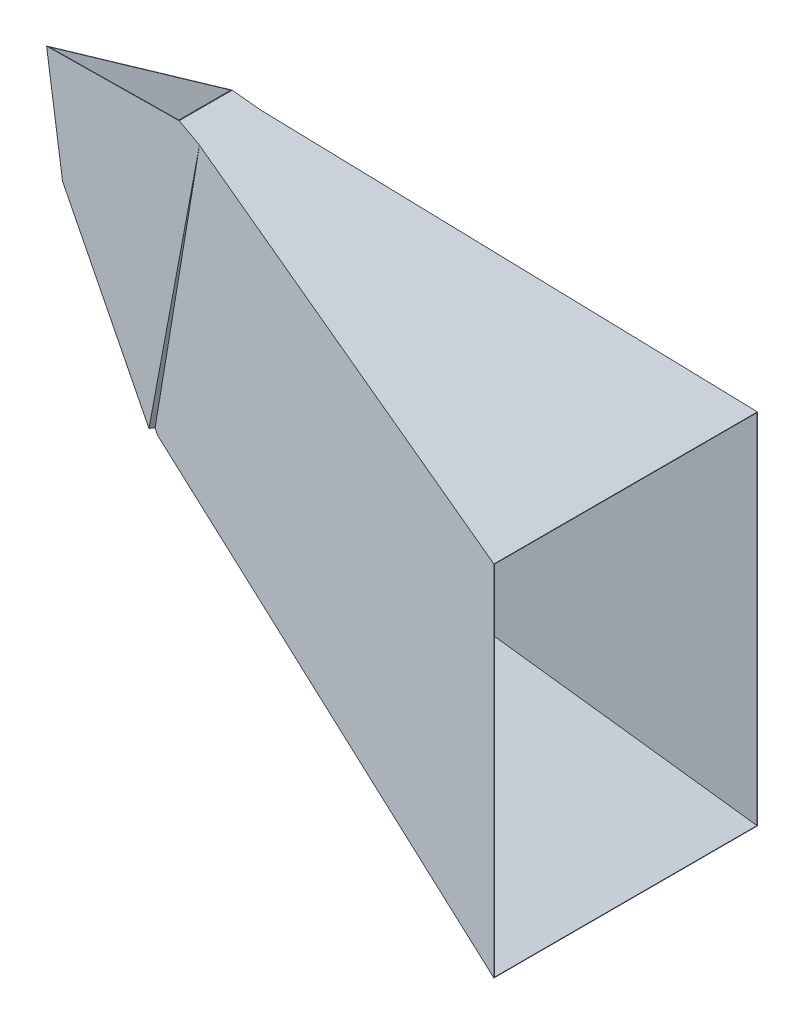
SolidWorks part; units mm, degrees
ref_plane "Front Plane" through (0, 0, 0) normal (0, 0, 1) x (1, 0, 0)
ref_plane "Top Plane" through (0, 0, 0) normal (0, 1, 0) x (1, 0, 0)
ref_plane "Right Plane" through (0, 0, 0) normal (1, 0, 0) x (0, 0, -1)
sketch "Sketch1" plane through (0, 0, 0) normal (0, 0, 1) x (1, 0, 0)
  line L0 (0, 0) -> (-2819.61, 1161.48)
  line L1 (-2819.61, 1161.48) -> (-3490.66, 2155.96)
  line L2 (-3490.66, 2155.96) -> (-3609.78, 2815.96)
  line L3 (0, 0) -> (0, 2235)
  line L4 (0, 2235) -> (-2618, 2991)
  line L5 (-2618, 2991) -> (-3609.78, 2815.96)
  dimension "D1" = 2819.61
  dimension "D2" = 1161.48
  dimension "D3" = 994.48
  dimension "D4" = 671.05
  dimension "D5" = 660
  dimension "D6" = 119.12
  dimension "D7" = 2235
  dimension "D8" = 2618
  dimension "D9" = 756
extrude "Boss-Extrude1" add sketch "Sketch1" along normal blind 821.33 and the other way blind 821.33
ref_plane "Plane1" through (-3609.78, 0, 0) normal (1, 0, 0) x (0, 0, -1)
sketch "Sketch3" plane through (0, 0, 0) normal (-0.3809, -0.9246, 0) x (0.9246, -0.3809, 0)
  line L0 (-3049.4649, 0) -> (-3049.4649, 100)
  line L1 (-3049.4649, -821.33) -> (-3049.4649, 821.33) construction
  line L2 (-3049.4649, 0) -> (-3049.4649, -100)
  line L3 (0, 821.33) -> (-3049.4649, 100)
  line L4 (0, -821.33) -> (-3049.4649, -100)
  dimension "D1" = 100
ref_plane "Plane2" through (-197.2108, 0, 770.8783) normal (0.2478, 0, -0.9688) x (-0.9688, 0, -0.2478)
sketch "Sketch4" plane through (-197.2108, 0, 770.8783) normal (0.2478, 0, -0.9688) x (-0.9688, 0, -0.2478)
  line L0 (2731.6378, 1161.48) -> (2332.756, 2991)
  line L1 (2935.1998, 1161.48) -> (2528.0758, 1161.48) construction
  line L2 (2332.756, 2991) -> (-203.562, 2235)
  line L3 (-203.562, 2235) -> (-203.562, 0)
  line L4 (-203.562, 0) -> (2731.6378, 1161.48)
extrude "Cut-Extrude1" cut sketch "Sketch4" against normal blind 1930.33
ref_plane "Plane3" through (-197.2108, 0, -770.8783) normal (-0.2478, 0, -0.9688) x (-0.9688, 0, 0.2478)
sketch "Sketch5" plane through (-197.2108, 0, -770.8783) normal (-0.2478, 0, -0.9688) x (-0.9688, 0, 0.2478)
  line L0 (-203.562, 0) -> (-203.562, 2235)
  line L1 (-203.562, 2235) -> (2332.756, 2991)
  line L2 (2332.756, 2991) -> (2706.8534, 1161.48)
  line L3 (-203.562, 0) -> (2706.8534, 1161.48) construction
  line L4 (2706.8534, 1161.48) -> (-203.562, 0)
extrude "Cut-Extrude2" cut sketch "Sketch5" along normal blind 3500.33
sketch "Sketch6" plane through (-591.0222, 3348.7428, 0) normal (-0.1738, 0.9848, 0) x (0.9848, 0.1738, 0)
  line L0 (-3065.4129, 0) -> (-1916.1408, 190.4918)
  line L1 (-3065.4129, 821.33) -> (-3065.4129, -821.33) construction
  line L2 (-1916.1408, 190.4918) -> (-1916.1408, 1255.1015)
  line L3 (-1916.1408, 1255.1015) -> (-3065.4129, 1255.1015)
  line L4 (-3065.4129, 1255.1015) -> (-3065.4129, 0)
  line L5 (-3065.4129, -1489.9437) -> (-2058.3049, -1489.9437)
  line L6 (-2058.3049, -1489.9437) -> (-1916.6486, -190.3528)
  line L7 (-3065.4129, 0) -> (-3065.4129, -1489.9437)
  line L8 (-1916.6486, -190.3528) -> (-3065.4129, 0)
sketch "Sketch7" plane through (0, 0, 0) normal (0, 1, 0) x (1, 0, 0)
  line L0 (-3609.78, 0) -> (-2465.8862, 190.4918)
  line L1 (-2465.8862, 190.4918) -> (-2674.0673, 1440.6089)
  line L2 (-2674.0673, 1440.6089) -> (-3609.78, 1440.6089)
  line L3 (-3609.78, 1440.6089) -> (-3609.78, 0)
  line L4 (-3609.78, 0) -> (-3609.78, -1179.2038)
  line L5 (-3609.78, 0) -> (-3609.78, -1489.9437) construction
  line L6 (-3609.78, -1179.2038) -> (-2465.8862, -1179.2038)
  line L7 (-2465.8862, -1179.2038) -> (-2466.4296, -190.3528)
  line L8 (-2466.4296, -190.3528) -> (-3609.78, 0)
extrude "Cut-Extrude4" cut sketch "Sketch7" along normal blind 3500.33 contours L7 L8 L4 L6 | L2 L3 L0 L1 region at (-3098.9949, 0, -743.0567) region at (-3054.7081, 0, 635.8437)
shell "Shell1" thickness 2.5 removed face at (-2948.5933, 2932.6533, -0.014) removed face at (0, 1117.5, 0)
